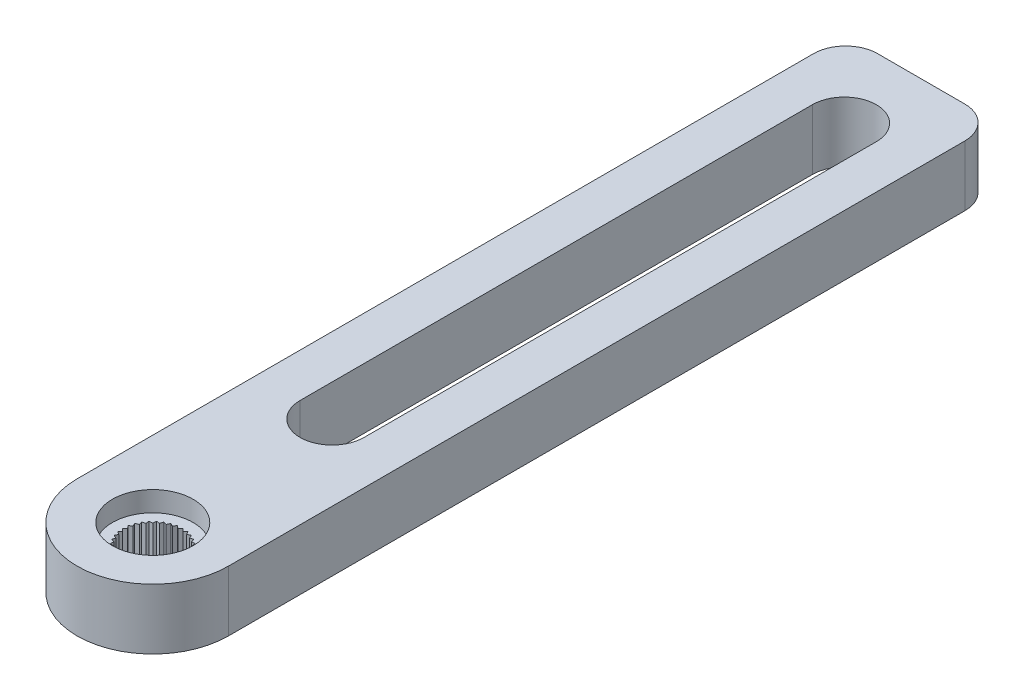
SolidWorks part; units mm, degrees
ref_plane "Alzado" through (0, 0, 0) normal (0, 0, 1) x (1, 0, 0)
ref_plane "Planta" through (0, 0, 0) normal (0, 1, 0) x (1, 0, 0)
ref_plane "Vista lateral" through (0, 0, 0) normal (1, 0, 0) x (0, 0, -1)
sketch "Croquis1" plane through (0, 0, 0) normal (0, 1, 0) x (1, 0, 0)
  line L0 (7.5, 0) -> (7.5, 76.2)
  line L1 (-7.5, 0) -> (-7.5, 76.2)
  line L2 (-7.5, 76.2) -> (7.5, 76.2)
  line L3 (0, 68.58) -> (0, 17.78) construction
  line L4 (3.175, 68.58) -> (3.175, 17.78)
  line L5 (-3.175, 68.58) -> (-3.175, 17.78)
  line L7 (0, 0) -> (-2.7555, 0)
  line L8 (0, 0) -> (-3.7911, 0.3317)
  line L9 (0, 0) -> (-3.1184, 0.5499)
  line L10 (-3, 0) -> (-2.7395, 0.2397)
  line L11 (-2.7395, 0.2397) -> (-2.9544, 0.5209)
  circle A0 centre (0, 0) radius 3
  circle A1 centre (0, 0) radius 4
  arc A2 (3.175, 68.58) -> (-3.175, 68.58) centre (0, 68.58) ccw
  circle A3 centre (0, 0) radius 7.5
  arc A4 (-3.175, 17.78) -> (3.175, 17.78) centre (0, 17.78) ccw
  circle A8 centre (0, 0) radius 7
  circle A9 centre (0, 0) radius 2.75
  point P11 (0, 43.18)
  dimension "D2" = 76.2
  dimension "D3" = 7.62
  dimension "D4" = 3.175
  dimension "D5" = 50.8
  dimension "D16" = 5.5
  dimension "D14" = 10
  dimension "D15" = 5
  dimension "D12" = 0.5
extrude "Saliente-Extruir1" add sketch "Croquis1" along normal blind 4 contours A3 | A3 A1 | A1 A0 | A8 A1 | A8 A3 | A3 | A3 | A3 region at (0, 0, -8.2766) region at (0, 0, 7.2879) region at (-3.8869, 0, 0) region at (-6.802, 0, 0)
extrude "Saliente-Extruir2" add sketch "Croquis1<3>" along normal blind 6 contours A8 A3 | A3 | A8 A1 region at (0, 0, -8.2766) region at (0, 0, 7.2879) region at (-6.802, 0, 0)
sketch "Croquis1<3>" plane through (0, 0, 0) normal (0, 1, 0) x (1, 0, 0) same geometry as "Croquis1"
extrude "Saliente-Extruir3" add sketch "Croquis1<4>" along normal blind 4 contours L8 A0 L10 | L11 A0 L8 region at (-2.9107, 0, -0.1665) region at (-2.8954, 0, -0.3415)
sketch "Croquis1<4>" plane through (0, 0, 0) normal (0, 1, 0) x (1, 0, 0) same geometry as "Croquis1"
pattern_circular "MatrizC1" count 37 every 10 about axis through (0, 6, 0) along (0, -1, 0) of "Saliente-Extruir3"
fillet "Fillet1" radius 3.175 2 edges at (-7.5, 3, -76.2) (7.5, 3, -76.2)
equation "\"A\"= 3"
equation "\"B\"= 2"
